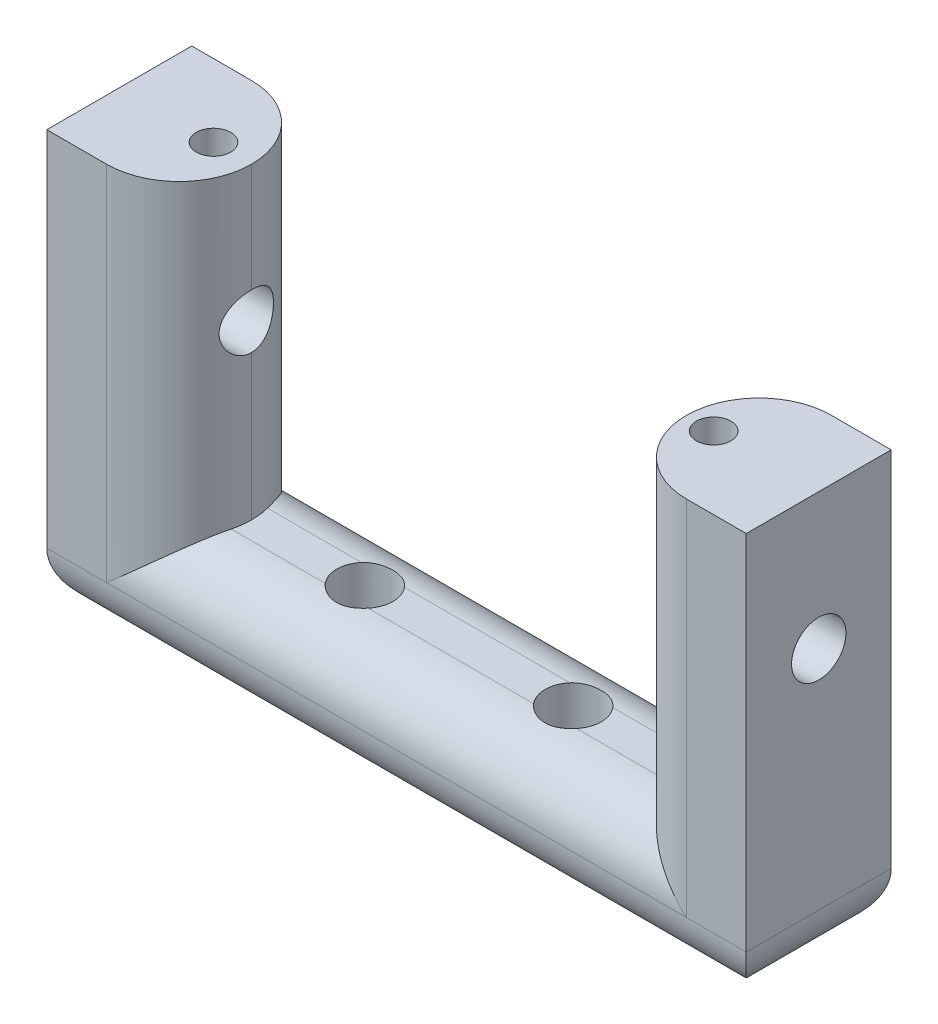
SolidWorks part; units mm, degrees
material "ABS"
ref_plane "Plan de face" through (0, 0, 0) normal (0, 0, 1) x (1, 0, 0)
ref_plane "Plan de dessus" through (0, 0, 0) normal (0, 1, 0) x (1, 0, 0)
ref_plane "Plan de droite" through (0, 0, 0) normal (1, 0, 0) x (0, 0, -1)
sketch "Esquisse4" plane through (0, 0, 0) normal (0, 1, 0) x (1, 0, 0)
  line L0 (12, -4) -> (19.3, -4)
  line L1 (19.3, 4) -> (19.3, -4)
  line L2 (19.3, 4) -> (12, 4)
  line L3 (0, 0) -> (0, -7.8629) construction
  line L4 (-19.3, 4) -> (-12, 4)
  line L5 (-19.3, 4) -> (-19.3, -4)
  line L6 (-12, -4) -> (-19.3, -4)
  line L10 (12, 4) -> (12, -4)
  line L12 (-12, 4) -> (-12, -4)
  circle A0 centre (14.5, 0) radius 0.8 construction
  circle A1 centre (-13.1, 0) radius 0.8 construction
  point P6 (0, 0)
  dimension "D2" = 1.6
  dimension "D7" = 2.5
  dimension "D5" = 4
  dimension "D1" = 27.6
  dimension "D3" = 8
  dimension "D4" = 7.3
  dimension "D6" = 4
  dimension "D8" = 4
  dimension "D9" = 12
extrude "MIP_SERVO" add sketch "Esquisse4" against normal blind 23
sketch "Esquisse14" plane through (0, 0, 0) normal (0, 1, 0) x (1, 0, 0)
  line L0 (-12, -4) -> (-12, 4) construction
  line L1 (-12, 4) -> (-19.3, 4) construction
  line L2 (19.3, 4) -> (12, 4) construction
  circle A0 centre (13.5, 0) radius 0.95
  circle A1 centre (-14.1, 0) radius 0.95
  dimension "D2" = 1.9
  dimension "D1" = 27.6
  dimension "D3" = 2.1
  dimension "D4" = 4
  dimension "D5" = 4
extrude "MAP_SERVO" cut sketch "Esquisse14" against normal blind 5
sketch "Esquisse6" plane through (0, -23, 0) normal (0, -1, 0) x (1, 0, 0)
  line L6 (12, 4) -> (-12, 4)
  line L7 (12, 4) -> (12, -4)
  line L8 (12, -4) -> (-12, -4)
  line L9 (-12, 4) -> (-12, -4)
extrude "FOND" add sketch "Esquisse6" against normal blind 6
sketch "Esquisse7" plane through (0, -17, 0) normal (0, 1, 0) x (1, 0, 0)
  line L0 (0, 0) -> (-5.75, 0) construction
  line L1 (0, 0) -> (5.75, 0) construction
  circle A0 centre (-5.75, 0) radius 1.55
  circle A1 centre (5.75, 0) radius 1.55
  dimension "D1" = 3.1
  dimension "D2" = 5.75
  dimension "D3" = 5.75
extrude "PIVOTS_BIELLES" cut sketch "Esquisse7" against normal through all
fillet "Fillet1" radius 4 4 edges
fillet "Fillet2" radius 3 6 edges at (19.3, -23, 0) (-19.3, -23, 0) (0, -23, -4) (0, -23, 4)
sketch "Sketch1" plane through (-19.3, 0, 0) normal (-1, 0, 0) x (0, 0, 1)
  line L1 (4, -20) -> (4, 0) construction
  line L2 (-4, 0) -> (4, 0) construction
  circle A0 centre (0, -7.5) radius 1.5
  dimension "D1" = 3
  dimension "D2" = 4
  dimension "D3" = 7.5
extrude "Cut-Extrude1" cut sketch "Sketch1" against normal blind 40 contours A0
